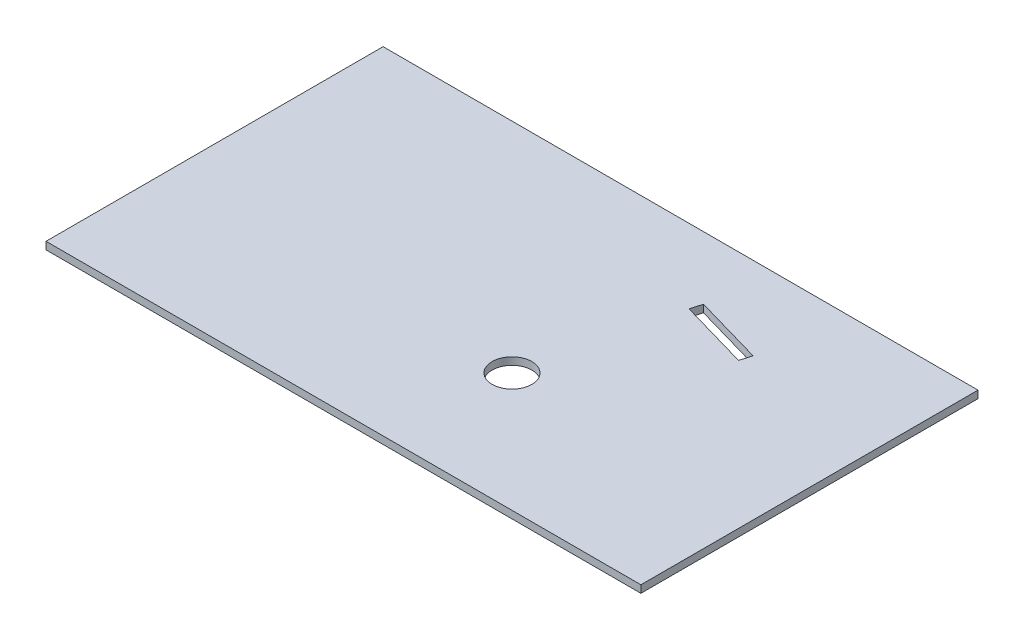
SolidWorks part; units mm, degrees
material "Particle Board"
ref_plane "Front Plane" through (0, 0, 0) normal (0, 0, 1) x (1, 0, 0)
ref_plane "Top Plane" through (0, 0, 0) normal (0, 1, 0) x (1, 0, 0)
ref_plane "Right Plane" through (0, 0, 0) normal (1, 0, 0) x (0, 0, -1)
sketch "Sketch3" plane through (0, 0, 0) normal (0, 1, 0) x (1, 0, 0)
  line L1 (0, 0) -> (-839.8654, 0) construction
  line L2 (0, 0) -> (-451.1992, 260.5) construction
  line L5 (-524, 0) -> (-525.5875, 0)
  line L6 (277.6777, 444.3772) -> (277.6777, 446.248)
  circle A0 centre (0, 0) radius 254 construction
  arc A3 (277.6777, 444.3772) -> (-524, 0) centre (0, 0) ccw
  arc A4 (277.6777, 446.248) -> (-525.5875, 0) centre (0, 0) ccw
  arc A5 (278.5189, 445.7235) -> (-525.5875, 0) centre (0, 0) ccw construction
  dimension "D1" = 524
  dimension "D2" = 1.5875
  dimension "D4" = 122
  dimension "D5" = 508
  dimension "D3" = 30
extrude "Boss-Extrude1" add sketch "Sketch3" along normal blind 50.8
sketch "Sketch4" plane through (0, 50.8, 0) normal (0, 1, 0) x (1, 0, 0)
  line L5 (-889, 558.8) -> (635, 558.8)
  line L6 (-889, 558.8) -> (-889, -304.8)
  line L7 (-889, -304.8) -> (635, -304.8)
  line L8 (635, 558.8) -> (635, -304.8)
  dimension "D1" = 304.8
  dimension "D2" = 1524
  dimension "D3" = 863.6
  dimension "D4" = 635
extrude "Boss-Extrude2" add sketch "Sketch4" along normal blind 19.05
hole_wizard "Ø20.0mm Dowel Hole1" positions "Sketch6" profile "Sketch7" hole size "Ø20.0" standard "ANSI Metric" end condition through all
sketch "Sketch6" plane through (0, 50.8, 0) normal (0, -1, 0) x (-1, 0, 0)
  point P0 (0, 0)
sketch "Sketch7" plane through (0, 50.8, 0) normal (1, 0, 0) x (0, 0, -1)
  line L0 (0, 0) -> (0, 19.05)
  line L1 (0, 19.05) -> (50.8, 19.05)
  line L2 (50.8, 19.05) -> (50.8, 0)
  line L5 (50.8, 0) -> (0, 0)
  line L11 (0, -6.35) -> (0, 107.95) construction
  dimension "Thru Hole Dia." = 101.6
  dimension "Thru Hole Depth" = 19.05
ref_plane "Plane1" through (0, 0, 298.45) normal (0, 0, 1) x (1, 0, 0)
sketch "Sketch8" plane through (0, 0, 0) normal (0, 0, 1) x (1, 0, 0)
  line L0 (-524, 50.8) -> (-524, 0) construction
  line L1 (-525.5875, 50.8) -> (-524, 50.8)
  line L2 (-525.5875, 50.8) -> (-525.5875, 0)
  line L3 (-525.5875, 0) -> (-524, 0)
  line L4 (-524, 50.8) -> (-524, 0)
  line L5 (-525.5875, 50.8) -> (-525.5875, 0) construction
  line L6 (-525.5875, 0) -> (-524, 0) construction
  line L7 (-525.5875, 50.8) -> (-524, 50.8) construction
extrude "Boss-Extrude3" add sketch "Sketch8" along normal blind 204
sketch "Sketch9" plane through (0, 50.8, 0) normal (0, -1, 0) x (-1, 0, 0)
  line L0 (-92.8177, 397.8388) -> (-270.6511, 346.8459)
  line L1 (-270.6511, 346.8459) -> (-262.382, 318.008)
  line L2 (-262.382, 318.008) -> (-84.5486, 369.0009)
  line L3 (-84.5486, 369.0009) -> (-92.8177, 397.8388)
  line L6 (0, 0) -> (-635, 0) construction
  line L7 (-635, -304.8) -> (-635, 558.8) construction
  dimension "D1" = 185
  dimension "D2" = 30
  dimension "D3" = 16
  dimension "D4" = 262.382
  dimension "D5" = 318.008
extrude "Cut-Extrude1" cut sketch "Sketch9" against normal through all
sketch "Sketch10" plane through (0, 69.85, 0) normal (0, -1, 0) x (-1, 0, 0)
  line L0 (0, 0) -> (-545.6, 0) construction
  line L1 (0, 0) -> (277.6777, 444.3772) construction
  line L2 (0, 0) -> (195.5256, 509.3615) construction
  line L3 (0, 0) -> (94.7424, 537.3111) construction
  circle A0 centre (0, 0) radius 545.6 construction
  dimension "D1" = 11
  dimension "D2" = 11
ref_axis "WHEEL CENTER" through (-565.7508, 50.8, 0) along (1, 0, 0)
ref_plane "BASE CENTER" through (-127, 0, 0) normal (1, 0, 0) x (0, 0, -1)
